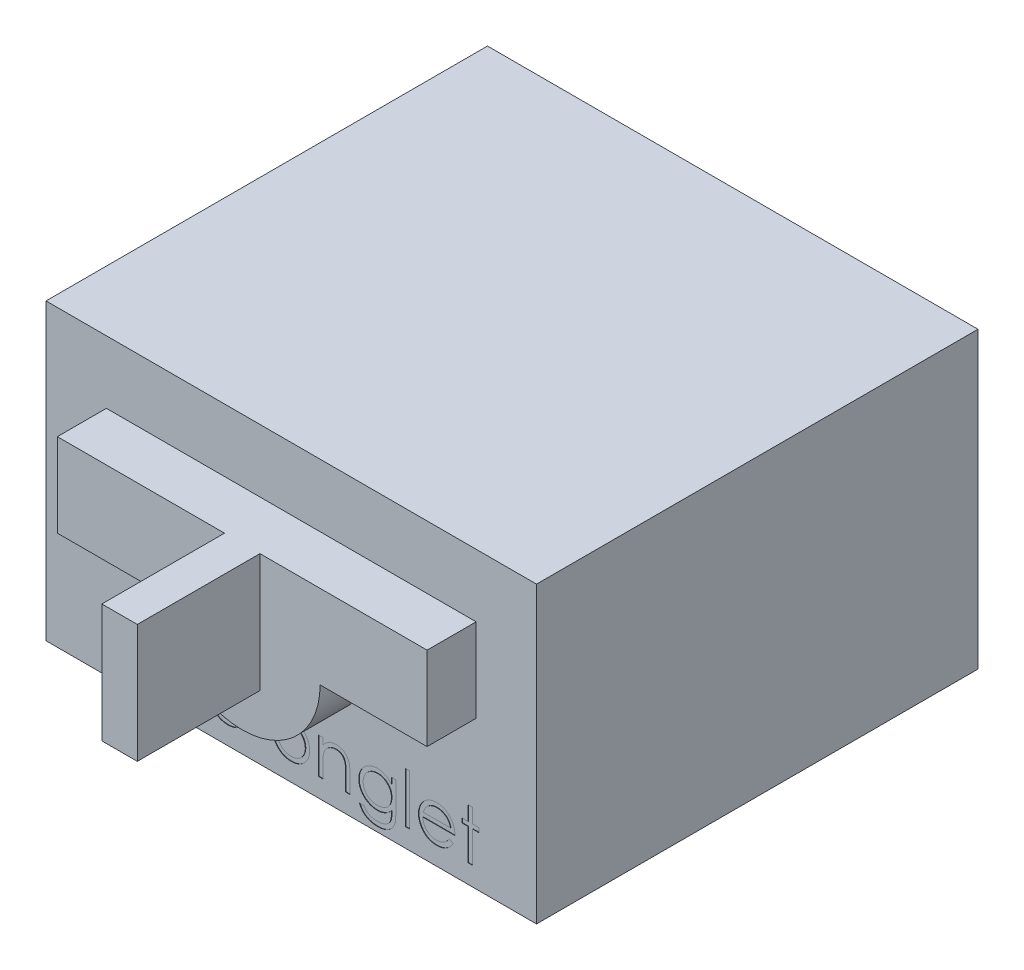
SolidWorks part; units mm, degrees
ref_plane "Front" through (0, 0, 0) normal (0, 0, 1) x (1, 0, 0)
ref_plane "Top" through (0, 0, 0) normal (0, 1, 0) x (1, 0, 0)
ref_plane "Right" through (0, 0, 0) normal (1, 0, 0) x (0, 0, -1)
sketch "Esquisse1" plane through (0, 0, 0) normal (0, 0, 1) x (1, 0, 0)
  line L1 (0, 0) -> (1000, 0)
  line L2 (0, 0) -> (0, 600)
  line L3 (0, 600) -> (1000, 600)
  line L4 (1000, 0) -> (1000, 600)
  dimension "D1" = 1000
  dimension "D2" = 600
extrude "Boss.-Extru.1" add sketch "Esquisse1" along normal blind 900
sketch "Esquisse2" plane through (0, 0, 900) normal (0, 0, 1) x (1, 0, 0)
  line L0 (123.1347, 471.9157) -> (123.1347, 301.5488)
  line L1 (123.1347, 301.5488) -> (341.1326, 301.5488)
  line L2 (341.1326, 301.5488) -> (658.8674, 301.5488) construction
  line L3 (500, 301.5488) -> (500, 142.6813) construction
  line L4 (500, 301.5488) -> (500, 600) construction
  line L5 (1000, 600) -> (0, 600) construction
  line L6 (123.1347, 471.9157) -> (876.8653, 471.9157)
  line L7 (876.8653, 301.5488) -> (658.8674, 301.5488)
  line L8 (876.8653, 471.9157) -> (876.8653, 301.5488)
  arc A0 (341.1326, 301.5488) -> (658.8674, 301.5488) centre (500, 301.5488) ccw
  point P5 (84.9319, 318.0689)
  point P10 (123.1347, 301.5488)
  point P13 (500, 471.9157)
extrude "Boss.-Extru.2" add sketch "Esquisse2" along normal blind 100
sketch "Esquisse3" plane through (0, 0, 1000) normal (0, 0, 1) x (1, 0, 0)
  line L0 (876.8653, 471.9157) -> (123.1347, 471.9157) construction
  line L1 (463.8622, 471.9157) -> (536.1378, 471.9157)
  line L2 (463.8622, 471.9157) -> (463.8622, 230.1271)
  line L3 (463.8622, 230.1271) -> (536.1378, 230.1271)
  line L4 (536.1378, 471.9157) -> (536.1378, 230.1271)
  line L5 (500, 230.1271) -> (500, 471.9157) construction
extrude "Boss.-Extru.3" add sketch "Esquisse3" along normal blind 250
sketch "Esquisse4" plane through (0, 0, 900) normal (0, 0, 1) x (1, 0, 0)
  text T0 "Scie onglet" font "Century Gothic" height 100
extrude "Enlèv. mat.-Extru.1" cut sketch "Esquisse4" against normal blind 1
